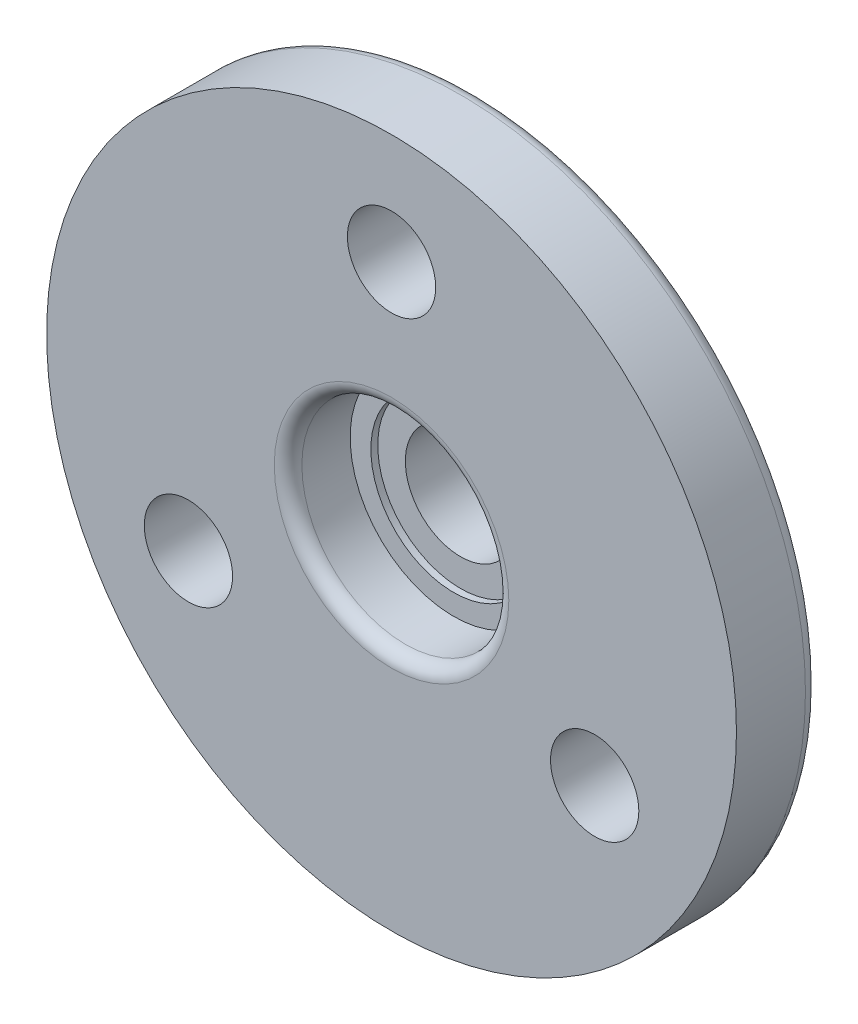
SolidWorks part; units mm, degrees
ref_plane "Ebene vorne" through (0, 0, 0) normal (0, 0, 1) x (1, 0, 0)
ref_plane "Ebene oben" through (0, 0, 0) normal (0, 1, 0) x (1, 0, 0)
ref_plane "Ebene rechts" through (0, 0, 0) normal (1, 0, 0) x (0, 0, -1)
sketch "Skizze2" plane through (0, 0, 0) normal (1, 0, 0) x (0, 0, -1)
  line L0 (0, 0) -> (99, 0) construction
  line L1 (9.5, 7) -> (8.5, 7) construction
  line L2 (9.5, 15) -> (9.5, 5) construction
  line L3 (18.5, 5) -> (9.5, 5) construction
  line L4 (18.5, 4) -> (18.5, 5) construction
  line L5 (18.5, 4) -> (7.5, 4) construction
  line L6 (7.5, 4) -> (7.5, 6) construction
  line L7 (7.5, 6) -> (7, 6) construction
  line L8 (7, 7.5) -> (7, 3) construction
  line L10 (7, 7.5) -> (2, 7.5) construction
  line L11 (2.5, 7.5) -> (2.5, 25) construction
  line L12 (8.5, 7) -> (8.5, 25) construction
  line L13 (0, 25) -> (99, 25) construction
  line L14 (0, 0) -> (99, 0) construction
  line L15 (9.5, 7) -> (8.5, 7)
  line L16 (9.5, 7) -> (9.5, 5)
  line L17 (18.5, 5) -> (9.5, 5)
  line L18 (18.5, 4) -> (18.5, 5)
  line L19 (18.5, 4) -> (7.5, 4)
  line L20 (7.5, 4) -> (7.5, 6)
  line L21 (7.5, 6) -> (7, 6)
  line L22 (7, 7.5) -> (7, 6)
  line L24 (7, 7.5) -> (2.5, 7.5)
  line L25 (2.5, 7.5) -> (2.5, 25)
  line L26 (8.5, 7) -> (8.5, 25)
  line L27 (2.5, 25) -> (8.5, 25)
revolve "Rotation1" add sketch "Skizze2" angle 360 about L14
sketch "Skizze3" plane through (0, 0, -2.5) normal (0, 0, 1) x (1, 0, 0)
  circle A0 centre (0, 0) radius 17 construction
  point P4 (0, 17)
hole_wizard "Ø6.4 (6.4) Durchmesser Bohrung1" positions "Skizze3" profile "Skizze4" hole size "Ø6.4" standard "DIN"
sketch "Skizze4" plane through (0, 17, -2.5) normal (1, 0, 0) x (0, -1, 0)
  line L0 (0, 0) -> (0, 11.4228)
  line L1 (0, 11.4228) -> (3.2, 9.5)
  line L2 (3.2, 9.5) -> (3.2, 0)
  line L5 (3.2, 0) -> (0, 0)
  line L10 (0, 11.4228) -> (-3.2, 9.5) construction
  line L11 (0, -6.35) -> (0, 107.95) construction
  dimension "Bohrerdurchmesser" = 6.4
  dimension "Bohrungstiefe" = 9.5
  dimension "Spitzenwinkel" = 118
pattern_circular "Kreismuster1" count 3 over 360 of "Ø6.4 (6.4) Durchmesser Bohrung1" reverse direction yes
fillet "Verrundung1" radius 1 3 edges at (5, 0, -18.5) (25, 0, -8.5) (7.5, 0, -2.5)
